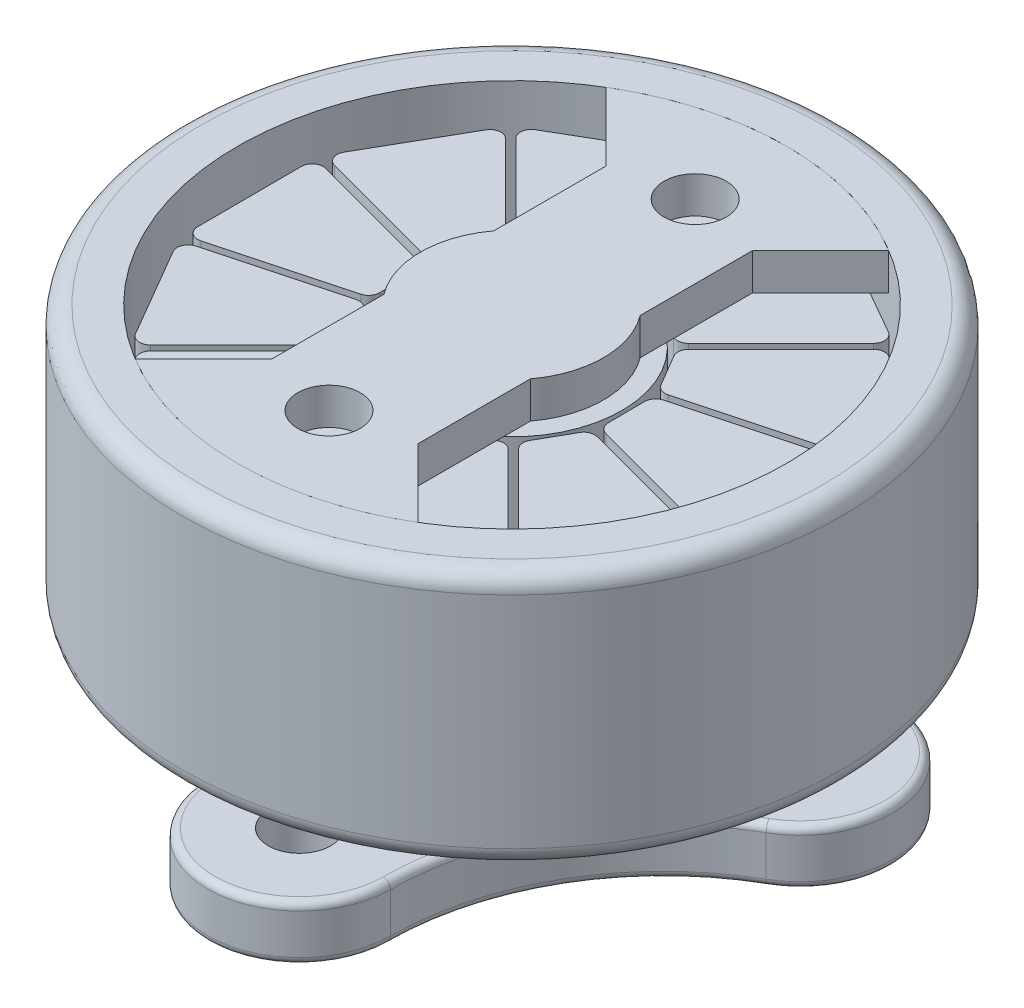
SolidWorks part; units mm, degrees
ref_plane "前视基准面" through (0, 0, 0) normal (0, 0, 1) x (1, 0, 0)
ref_plane "上视基准面" through (0, 0, 0) normal (0, 1, 0) x (1, 0, 0)
ref_plane "右视基准面" through (0, 0, 0) normal (1, 0, 0) x (0, 0, -1)
other "Configuration Table"
sketch "草图1" plane through (0, 0, 0) normal (0, 1, 0) x (1, 0, 0)
  circle A0 centre (0, 0) radius 9
  dimension "D1" = 18
extrude "凸台-拉伸1" add sketch "草图1" along normal blind 7
sketch "草图2" plane through (0, 0, 0) normal (0, -1, 0) x (1, 0, 0)
  circle A0 centre (0, 0) radius 3
  dimension "D1" = 6
extrude "凸台-拉伸2" add sketch "草图2" along normal blind 2.5
sketch "草图3" plane through (0, -2.5, 0) normal (0, -1, 0) x (1, 0, 0)
  arc A0 (-6.2459, -0.7564) -> (-2.532, 5.7595) centre (-10.0319, 5.7179) ccw
  arc A1 (2.4679, 5.7873) -> (-2.532, 5.7595) centre (-0.032, 5.7734) ccw
  arc A2 (-6.2459, -0.7564) -> (-3.7219, -5.0726) centre (-4.9839, -2.9145) ccw
  arc A3 (3.778, -5.0309) -> (6.2539, -0.687) centre (5.0159, -2.859) ccw
  arc A4 (3.778, -5.0309) -> (-3.7219, -5.0726) centre (0.0641, -11.5468) ccw
  arc A5 (2.4679, 5.7873) -> (6.2539, -0.687) centre (9.9678, 5.8289) ccw
  point P18 (0, 0)
  dimension "D1" = 5
  dimension "D2" = 5
  dimension "D3" = 5
  dimension "D4" = 15
  dimension "D5" = 3
extrude "凸台-拉伸3" add sketch "草图3" along normal blind 1.5
sketch "草图4" plane through (0, -4, 0) normal (0, -1, 0) x (1, 0, 0)
  circle A0 centre (-0.032, 5.7734) radius 0.85
  circle A1 centre (5.0159, -2.859) radius 0.85
  circle A2 centre (-4.9839, -2.9145) radius 0.85
  point P9 (0, 0)
  dimension "D1" = 1.7
  dimension "D2" = 3
extrude "切除-拉伸1" cut sketch "草图4" against normal up to next
fillet "圆角1" radius 0.5 2 edges at (0, 0, 9) (0, 7, 9)
fillet "圆角5" radius 0.2 12 edges at (0.0225, -2.5, -4.0469) (-7.142, -2.5, -4.1765) (-3.516, -2.5, 2.004) (-0.0459, -2.5, 8.2734) (3.4935, -2.5, 2.0429) (7.1879, -2.5, -4.0969) (0.0225, -4, -4.0469) (-7.142, -4, -4.1765) (-3.516, -4, 2.004) (-0.0459, -4, 8.2734) (3.4935, -4, 2.0429) (7.1879, -4, -4.0969)
sketch "草图5" plane through (0, 7, 0) normal (0, 1, 0) x (1, 0, 0)
  circle A0 centre (0, 0) radius 7.5
  dimension "D1" = 15
extrude "切除-拉伸2" cut sketch "草图5" against normal up to surface (7 mm away) up to face at (0, 0, 8.5)
sketch "草图6" plane through (0, 7, 0) normal (0, 1, 0) x (1, 0, 0)
  line L0 (0, -7.5) -> (0, 7.5)
  line L5 (2, -7.5) -> (2, 7.5)
  line L8 (-2, -7.5) -> (-2, 7.5)
  line L9 (-2, 4.5714) -> (-3.8594, 6.4308)
  line L10 (2, 4.5714) -> (3.8594, 6.4308)
  line L13 (-6.05, 0) -> (6.05, 0) construction
  line L14 (2, -4.5714) -> (3.8594, -6.4308)
  line L15 (-2, -4.5714) -> (-3.8594, -6.4308)
  circle A5 centre (0, 0) radius 7.5
  circle A6 centre (0, 0) radius 2.5
  point P6 (0, 0)
  circle M7 centre (0, 0) radius 7.5
  dimension "D1" = 5
  dimension "D2" = 2
  dimension "D3" = 2
sketch "草图7" plane through (0, 7, 0) normal (0, 1, 0) x (1, 0, 0)
  circle A0 centre (0, 5) radius 0.85
  circle A1 centre (0, -5) radius 0.85
  point P6 (0, 0)
  dimension "D1" = 1.7
  dimension "D2" = 1.7
extrude "凸台-拉伸6" add sketch "草图6" against normal blind 1 separate body contours L8 A6 | L0 A6 L8 | L0 A6 L5 | L5 A6 | A6 L8 L0 M7 | L8 L15 M7 | A6 L0 L5 M7 | L14 L5 M7 | A6 L5 L0 M7 | A6 L0 L8 M7 | L9 L8 M7 | L5 L10 M7 region at (-1.0215, 7, 4.7973) region at (1.0215, 7, 4.7973) region at (-0.9285, 7, 0) region at (0.9285, 7, 0) region at (-2.6314, 7, 6.105) region at (2.6314, 7, 6.105) region at (-1.0215, 7, -4.7973) region at (1.0215, 7, -4.7973) region at (-2.2018, 7, 0) region at (2.2018, 7, 0) region at (-2.6314, 7, -6.105) region at (2.6314, 7, -6.105)
sketch "草图8" plane through (0, 0, 0) normal (0, 1, 0) x (1, 0, 0)
  circle A1 centre (0, 0) radius 3
  circle A2 centre (0, 0) radius 3
  dimension "D1" = 0
extrude "凸台-拉伸5" add sketch "草图8" along normal blind 6
extrude "切除-拉伸4" cut sketch "草图7" against normal up to next (1 mm away)
ref_axis "基准轴1" through (0, -4.55, 0) along (0, 1, 0)
sketch "草图12" plane through (0, 0, 0) normal (0, -1, 0) x (1, 0, 0)
  line L15 (-1.393, 7.1494) -> (1.4467, 7.1394)
  line L16 (0.8127, 3.3181) -> (1.7354, 6.7618)
  line L17 (0.5204, 3.0957) -> (-0.4734, 3.1041)
  line L18 (-0.7606, 3.3265) -> (-1.6838, 6.7717)
  line L19 (2.3683, 6.888) -> (4.8226, 5.4596)
  line L20 (2.3628, 2.4672) -> (4.8838, 4.9882)
  line L21 (1.9985, 2.4208) -> (1.1421, 2.9249)
  line L22 (1.0045, 3.2611) -> (1.9276, 6.7064)
  line L23 (5.495, 4.781) -> (6.9063, 2.3168)
  line L24 (3.2799, 0.9552) -> (6.7236, 1.878)
  line L25 (2.9412, 1.0972) -> (2.4515, 1.962)
  line L26 (2.5005, 2.322) -> (5.0226, 4.8441)
  line L27 (7.1494, 1.393) -> (7.1394, -1.4467)
  line L28 (3.3181, -0.8127) -> (6.7618, -1.7354)
  line L29 (3.0957, -0.5204) -> (3.1041, 0.4734)
  line L30 (3.3265, 0.7606) -> (6.7717, 1.6838)
  line L31 (6.888, -2.3683) -> (5.4596, -4.8226)
  line L32 (2.4672, -2.3628) -> (4.9882, -4.8838)
  line L33 (2.4208, -1.9985) -> (2.9249, -1.1421)
  line L34 (3.2611, -1.0045) -> (6.7064, -1.9276)
  line L35 (4.781, -5.495) -> (2.3168, -6.9063)
  line L36 (0.9552, -3.2799) -> (1.878, -6.7236)
  line L37 (1.0972, -2.9412) -> (1.962, -2.4515)
  line L38 (2.322, -2.5005) -> (4.8441, -5.0226)
  line L39 (1.393, -7.1494) -> (-1.4467, -7.1394)
  line L40 (-0.8127, -3.3181) -> (-1.7354, -6.7618)
  line L41 (-0.5204, -3.0957) -> (0.4734, -3.1041)
  line L42 (0.7606, -3.3265) -> (1.6838, -6.7717)
  line L43 (-2.3683, -6.888) -> (-4.8226, -5.4596)
  line L44 (-2.3628, -2.4672) -> (-4.8838, -4.9882)
  line L45 (-1.9985, -2.4208) -> (-1.1421, -2.9249)
  line L46 (-1.0045, -3.2611) -> (-1.9276, -6.7064)
  line L47 (-5.495, -4.781) -> (-6.9063, -2.3168)
  line L48 (-3.2799, -0.9552) -> (-6.7236, -1.878)
  line L49 (-2.9412, -1.0972) -> (-2.4515, -1.962)
  line L50 (-2.5005, -2.322) -> (-5.0226, -4.8441)
  line L51 (-7.1494, -1.393) -> (-7.1394, 1.4467)
  line L52 (-3.3181, 0.8127) -> (-6.7618, 1.7354)
  line L53 (-3.0957, 0.5204) -> (-3.1041, -0.4734)
  line L54 (-3.3265, -0.7606) -> (-6.7717, -1.6838)
  line L55 (-6.888, 2.3683) -> (-5.4596, 4.8226)
  line L56 (-2.4672, 2.3628) -> (-4.9882, 4.8838)
  line L57 (-2.4208, 1.9985) -> (-2.9249, 1.1421)
  line L58 (-3.2611, 1.0045) -> (-6.7064, 1.9276)
  line L59 (-4.781, 5.495) -> (-2.3168, 6.9063)
  line L60 (-0.9552, 3.2799) -> (-1.878, 6.7236)
  line L61 (-1.0972, 2.9412) -> (-1.962, 2.4515)
  line L62 (-2.322, 2.5005) -> (-4.8441, 5.0226)
  arc A0 (0.8127, 3.3181) -> (0.5204, 3.0957) centre (0.5229, 3.3957) cw
  arc A1 (2.3683, 6.888) -> (1.9276, 6.7064) centre (2.2174, 6.6287) ccw
  arc A2 (4.8226, 5.4596) -> (4.8838, 4.9882) centre (4.6717, 5.2003) cw
  arc A3 (-0.7606, 3.3265) -> (-0.4734, 3.1041) centre (-0.4709, 3.4041) ccw
  arc A4 (1.4467, 7.1394) -> (1.7354, 6.7618) centre (1.4457, 6.8394) cw
  arc A5 (-1.393, 7.1494) -> (-1.6838, 6.7717) centre (-1.394, 6.8494) ccw
  arc A6 (2.3628, 2.4672) -> (1.9985, 2.4208) centre (2.1507, 2.6793) cw
  arc A7 (1.0045, 3.2611) -> (1.1421, 2.9249) centre (1.2943, 3.1835) ccw
  arc A8 (5.495, 4.781) -> (5.0226, 4.8441) centre (5.2347, 4.6319) ccw
  arc A9 (6.9063, 2.3168) -> (6.7236, 1.878) centre (6.6459, 2.1677) cw
  arc A10 (3.2799, 0.9552) -> (2.9412, 1.0972) centre (3.2022, 1.245) cw
  arc A11 (2.5005, 2.322) -> (2.4515, 1.962) centre (2.7126, 2.1098) ccw
  arc A12 (7.1494, 1.393) -> (6.7717, 1.6838) centre (6.8494, 1.394) ccw
  arc A13 (7.1394, -1.4467) -> (6.7618, -1.7354) centre (6.8394, -1.4457) cw
  arc A14 (3.3181, -0.8127) -> (3.0957, -0.5204) centre (3.3957, -0.5229) cw
  arc A15 (3.3265, 0.7606) -> (3.1041, 0.4734) centre (3.4041, 0.4709) ccw
  arc A16 (6.888, -2.3683) -> (6.7064, -1.9276) centre (6.6287, -2.2174) ccw
  arc A17 (5.4596, -4.8226) -> (4.9882, -4.8838) centre (5.2003, -4.6717) cw
  arc A18 (2.4672, -2.3628) -> (2.4208, -1.9985) centre (2.6793, -2.1507) cw
  arc A19 (3.2611, -1.0045) -> (2.9249, -1.1421) centre (3.1835, -1.2943) ccw
  arc A20 (4.781, -5.495) -> (4.8441, -5.0226) centre (4.6319, -5.2347) ccw
  arc A21 (2.3168, -6.9063) -> (1.878, -6.7236) centre (2.1677, -6.6459) cw
  arc A22 (0.9552, -3.2799) -> (1.0972, -2.9412) centre (1.245, -3.2022) cw
  arc A23 (2.322, -2.5005) -> (1.962, -2.4515) centre (2.1098, -2.7126) ccw
  arc A24 (1.393, -7.1494) -> (1.6838, -6.7717) centre (1.394, -6.8494) ccw
  arc A25 (-1.4467, -7.1394) -> (-1.7354, -6.7618) centre (-1.4457, -6.8394) cw
  arc A26 (-0.8127, -3.3181) -> (-0.5204, -3.0957) centre (-0.5229, -3.3957) cw
  arc A27 (0.7606, -3.3265) -> (0.4734, -3.1041) centre (0.4709, -3.4041) ccw
  arc A28 (-2.3683, -6.888) -> (-1.9276, -6.7064) centre (-2.2174, -6.6287) ccw
  arc A29 (-4.8226, -5.4596) -> (-4.8838, -4.9882) centre (-4.6717, -5.2003) cw
  arc A30 (-2.3628, -2.4672) -> (-1.9985, -2.4208) centre (-2.1507, -2.6793) cw
  arc A31 (-1.0045, -3.2611) -> (-1.1421, -2.9249) centre (-1.2943, -3.1835) ccw
  arc A32 (-5.495, -4.781) -> (-5.0226, -4.8441) centre (-5.2347, -4.6319) ccw
  arc A33 (-6.9063, -2.3168) -> (-6.7236, -1.878) centre (-6.6459, -2.1677) cw
  arc A34 (-3.2799, -0.9552) -> (-2.9412, -1.0972) centre (-3.2022, -1.245) cw
  arc A35 (-2.5005, -2.322) -> (-2.4515, -1.962) centre (-2.7126, -2.1098) ccw
  arc A36 (-7.1494, -1.393) -> (-6.7717, -1.6838) centre (-6.8494, -1.394) ccw
  arc A37 (-7.1394, 1.4467) -> (-6.7618, 1.7354) centre (-6.8394, 1.4457) cw
  arc A38 (-3.3181, 0.8127) -> (-3.0957, 0.5204) centre (-3.3957, 0.5229) cw
  arc A39 (-3.3265, -0.7606) -> (-3.1041, -0.4734) centre (-3.4041, -0.4709) ccw
  arc A40 (-6.888, 2.3683) -> (-6.7064, 1.9276) centre (-6.6287, 2.2174) ccw
  arc A41 (-5.4596, 4.8226) -> (-4.9882, 4.8838) centre (-5.2003, 4.6717) cw
  arc A42 (-2.4672, 2.3628) -> (-2.4208, 1.9985) centre (-2.6793, 2.1507) cw
  arc A43 (-3.2611, 1.0045) -> (-2.9249, 1.1421) centre (-3.1835, 1.2943) ccw
  arc A44 (-4.781, 5.495) -> (-4.8441, 5.0226) centre (-4.6319, 5.2347) ccw
  arc A45 (-2.3168, 6.9063) -> (-1.878, 6.7236) centre (-2.1677, 6.6459) cw
  arc A46 (-0.9552, 3.2799) -> (-1.0972, 2.9412) centre (-1.245, 3.2022) cw
  arc A47 (-2.322, 2.5005) -> (-1.962, 2.4515) centre (-2.1098, 2.7126) ccw
  point P146 (0, 0)
  dimension "D1" = 0.3
  dimension "D2" = 12
extrude "凸台-拉伸8" add sketch "草图12" against normal blind 6 separate body
